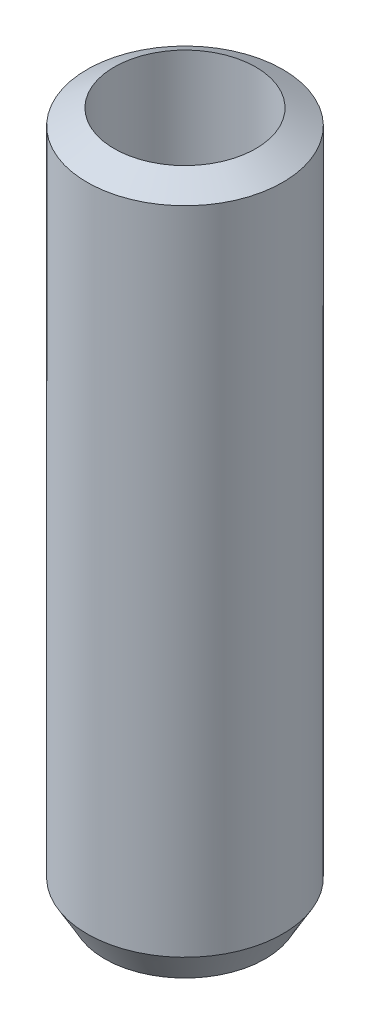
SolidWorks part; units mm, degrees
ref_plane "Front Plane" through (0, 0, 0) normal (0, 0, 1) x (1, 0, 0)
ref_plane "Top Plane" through (0, 0, 0) normal (0, 1, 0) x (1, 0, 0)
ref_plane "Right Plane" through (0, 0, 0) normal (1, 0, 0) x (0, 0, -1)
sketch "Sketch1" plane through (0, 0, 0) normal (0, 1, 0) x (1, 0, 0)
  circle A0 centre (0, 0) radius 15
  dimension "SHAFT_OD" = 30
extrude "Boss-Extrude1" add sketch "Sketch1" along normal blind 107.1437
sketch "Sketch2" plane through (0, 0, 0) normal (0, 1, 0) x (1, 0, 0)
  circle A0 centre (0, 0) radius 10.8521
  dimension "BORE_D" = 21.7042
extrude "Cut-Extrude1" cut sketch "Sketch2" along normal through all
chamfer "Chamfer1" distance 2.6941 angle 60 2 edges at (0, 107.1437, 15) (0, 0, 15) first distance on face at (0, 107.1437, 15) first distance on face at (0, 0, 10.8521)
